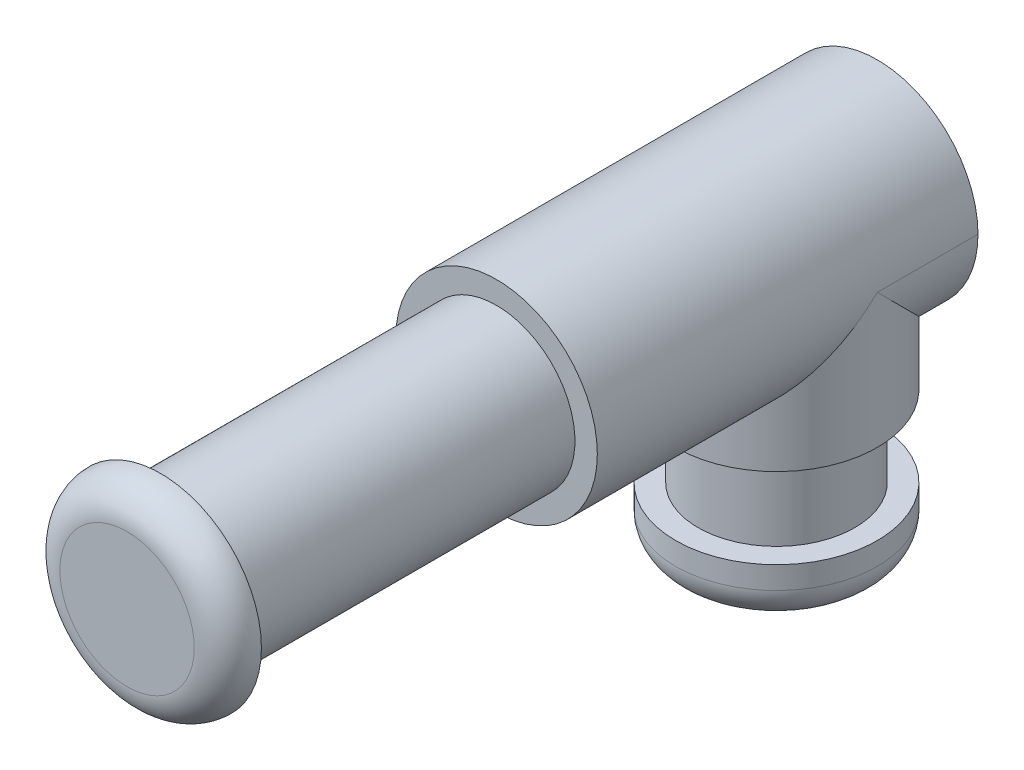
SolidWorks part; units mm, degrees
ref_plane "Front Plane" through (0, 0, 0) normal (0, 0, 1) x (1, 0, 0)
ref_plane "Top Plane" through (0, 0, 0) normal (0, 1, 0) x (1, 0, 0)
ref_plane "Right Plane" through (0, 0, 0) normal (1, 0, 0) x (0, 0, -1)
sketch "Sketch1" plane through (0, 0, 0) normal (0, 1, 0) x (1, 0, 0)
  circle A0 centre (0, 0) radius 22.86
  dimension "D1" = 45.72
extrude "Boss-Extrude9" add sketch "Sketch1" along normal blind 30.48
sketch "Sketch9" plane through (0, 0, 0) normal (0, -1, 0) x (1, 0, 0)
  circle A0 centre (0, 0) radius 17.78
  dimension "D1" = 35.56
extrude "Boss-Extrude10" add sketch "Sketch9" along normal blind 18.288
sketch "Sketch10" plane through (0, -18.288, 0) normal (0, -1, 0) x (1, 0, 0)
  circle A0 centre (0, 0) radius 22.86
extrude "Boss-Extrude11" add sketch "Sketch10" along normal blind 12.7
sketch "Sketch11" plane through (0, 0, 0) normal (0, 0, 1) x (1, 0, 0)
  line L0 (22.86, 30.48) -> (-22.86, 30.48) construction
  circle A0 centre (0, 30.48) radius 22.86
extrude "Boss-Extrude12" add sketch "Sketch11" along normal blind 63.5 and the other way blind 22.86
ref_point "Point6"
sketch "Sketch13" plane through (0, 0, 63.5) normal (0, 0, 1) x (1, 0, 0)
  circle A0 centre (0, 30.48) radius 17.78
  dimension "D1" = 35.56
extrude "Boss-Extrude13" add sketch "Sketch13" along normal blind 76.2
ref_point "Point7"
sketch "Sketch14" plane through (0, 0, 139.7) normal (0, 0, 1) x (1, 0, 0)
  circle A0 centre (0, 30.48) radius 22.86
extrude "Boss-Extrude14" add sketch "Sketch14" along normal blind 7.62
fillet "Fillet9" radius 7.62 1 edges at (22.86, 30.48, 147.32)
fillet "Fillet10" radius 7.62 1 edges at (0, -30.988, -22.86)
